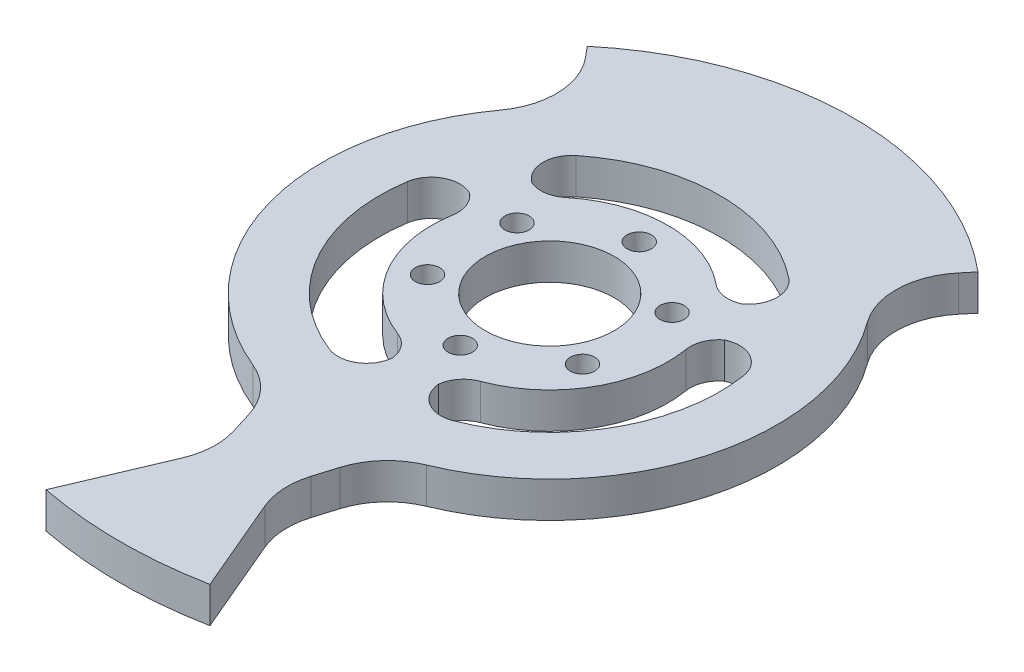
SolidWorks part; units mm, degrees
material "AISI Type A2 Tool Steel"
ref_plane "Front Plane" through (0, 0, 0) normal (0, 0, 1) x (1, 0, 0)
ref_plane "Top Plane" through (0, 0, 0) normal (0, 1, 0) x (1, 0, 0)
ref_plane "Right Plane" through (0, 0, 0) normal (1, 0, 0) x (0, 0, -1)
other "Center of Mass"
other "Bounding Box"
ref_plane "Default Plane" through (0, 2.286, 19.05) normal (0, -1, 0) x (-1, 0, 0)
sketch "Sketch1" plane through (0, 0, 0) normal (0, 1, 0) x (1, 0, 0)
  line L0 (0, -76.2) -> (0, -40.3225) construction
  line L1 (0, -40.3225) -> (0, -11.43) construction
  line L2 (0, -11.43) -> (0, 0) construction
  circle A0 centre (0, 0) radius 76.2 construction
  circle A1 centre (0, 0) radius 11.43
  arc A2 (0, -40.3225) -> (0, 40.3225) centre (0, 0) ccw
  arc A3 (0, 40.3225) -> (0, -76.2) centre (0, -17.9387) ccw construction
  arc A4 (0, 40.3225) -> (0, -40.3225) centre (0, 0) ccw
  dimension "D1" = 152.4
  dimension "D2" = 22.86
  dimension "D3" = 80.645
extrude "Boss-Extrude2" add sketch "Sketch1" along normal mid plane 6.35
sketch "Sketch9" plane through (0, 3.175, 0) normal (0, 1, 0) x (1, 0, 0)
  line L2 (-14.5396, -74.8) -> (-5.5514, -53.6249)
  line L3 (14.5396, -74.8) -> (5.5514, -53.6249)
  line L4 (0, -76.2) -> (0, 0) construction
  line L5 (-5.5514, -53.6249) -> (-10.0037, -39.0619)
  line L6 (5.5514, -53.6249) -> (10.0037, -39.0619)
  line L7 (-34.6536, 41.2986) -> (-25.9188, 30.8888)
  line L8 (34.6536, 41.2986) -> (25.9188, 30.8888)
  line L9 (0, 53.9115) -> (0, 0) construction
  line L10 (-5.5514, -53.6249) -> (0, -40.5467) construction
  line L11 (0, -40.5467) -> (5.5514, -53.6249) construction
  line L12 (-14.5396, -74.8) -> (0, 0) construction
  arc A5 (-14.5396, -74.8) -> (14.5396, -74.8) centre (0, 0) ccw
  arc A6 (-5.5514, -53.6249) -> (5.5514, -53.6249) centre (0, 0) ccw construction
  circle A7 centre (0, 0) radius 40.3225 construction
  arc A8 (-10.0037, -39.0619) -> (10.0037, -39.0619) centre (0, 0) ccw
  arc A9 (-34.6536, 41.2986) -> (34.6536, 41.2986) centre (0, 0) cw
  arc A10 (25.9188, 30.8888) -> (-25.9188, 30.8888) centre (0, 0) ccw
  dimension "D1" = 76.2
  dimension "D3" = 13.589
  dimension "D5" = 11
  dimension "D2" = 12
  dimension "D4" = 80
  dimension "D6" = 17
extrude "Boss-Extrude4" add sketch "Sketch9" against normal through all
sketch "Sketch6" plane through (0, 3.175, 0) normal (0, 1, 0) x (1, 0, 0)
  line L0 (-23.9377, 18.3511) -> (-15.7556, 13.8157)
  line L1 (15.7556, 13.8157) -> (23.9377, 18.3511)
  line L2 (0, 0) -> (-26.0927, 14.4634) construction
  line L3 (0, 0) -> (26.0927, 14.4634) construction
  line L4 (-23.9377, 18.3511) -> (-26.0927, 14.4634) construction
  line L5 (23.9377, 18.3511) -> (26.0927, 14.4634) construction
  line L6 (0, 0) -> (0, 40.3225) construction
  arc A0 (-15.7556, 13.8157) -> (15.7556, 13.8157) centre (0, 0) cw
  arc A1 (-23.9377, 18.3511) -> (23.9377, 18.3511) centre (0, 0) cw
  circle A2 centre (0, 0) radius 11.43 construction
  arc A4 (29.0716, 27.9418) -> (-0.0952, -40.3224) centre (0, 0) ccw construction
  arc A5 (10.0037, -39.0619) -> (25.9188, 30.8888) centre (0, 0) ccw construction
  dimension "D3" = 61
  dimension "D4" = 10.16
  dimension "D1" = 9.525
  dimension "D2" = 4.445
  dimension "D5" = 61
extrude "Cut-Extrude2" cut sketch "Sketch6" against normal through all
pattern_circular "CirPattern1" count 3 over 360 about axis through (0, 3.175, 0) along (0, -1, 0) of "Cut-Extrude2"
sketch "Sketch7" [suppressed] plane through (0, 6.35, 0) normal (0, 1, 0) x (1, 0, 0)
  line L0 (12.4559, 70.0208) -> (11.1213, 62.5185)
  line L1 (70.0208, -12.4559) -> (62.5185, -11.1213)
  line L2 (0, 0) -> (52.0712, 36.3433) construction
  line L3 (0, 0) -> (0, 63.5) construction
  line L4 (-6.2364, -4.3527) -> (0, 0) construction
  arc A0 (70.0208, -12.4559) -> (12.4559, 70.0208) centre (0, 0) ccw
  arc A1 (2.4423, -63.453) -> (0, 63.5) centre (0, 0) ccw construction
  arc A2 (62.5185, -11.1213) -> (11.1213, 62.5185) centre (0, 0) ccw
  dimension "D1" = 7.62
  dimension "D3" = 90
sketch "Sketch10" plane through (0, 3.175, 0) normal (0, 1, 0) x (1, 0, 0)
  line L0 (0, 20.955) -> (0, 15.875) construction
  line L1 (0, 15.875) -> (0, 11.43) construction
  circle A0 centre (0, 15.875) radius 2.159
  circle A1 centre (0, 15.875) radius 3.9624 construction
  circle A2 centre (0, 0) radius 11.43 construction
  arc A3 (4.0869, -20.5526) -> (19.8425, 6.7369) centre (0, 0) ccw construction
  dimension "D1" = 4.318
  dimension "D2" = 7.9248
  dimension "D3" = 15.875
extrude "Cut-Extrude3" cut sketch "Sketch10" against normal through all
pattern_circular "CirPattern8" count 6 over 360 about axis through (0, 3.175, 0) along (0, -1, 0) of "Cut-Extrude3" reverse direction yes
fillet "Fillet3" radius 5.08 12 edges at (-23.9377, 0, -18.3511) (23.9377, 0, -18.3511) (15.7556, 0, -13.8157) (-15.7556, 0, -13.8157) (3.9237, 0, 29.9062) (27.8614, 0, -11.5551) (19.8425, 0, -6.7369) (4.0869, 0, 20.5526) (-3.9237, 0, 29.9062) (-4.0869, 0, 20.5526) (-19.8425, 0, -6.7369) (-27.8614, 0, -11.5551)
other "Center of Mass Reference Point2"
fillet "Fillet4" radius 12.7 6 edges at (-5.5514, 0, 53.6249) (-10.0037, 0, 39.0619) (5.5514, 0, 53.6249) (10.0037, 0, 39.0619) (25.9188, 0, -30.8888) (-25.9188, 0, -30.8888)
sketch "Sketch13" plane through (0, 3.175, 0) normal (0, 1, 0) x (1, 0, 0)
  arc B0 (-18.8515, 23.5457) -> (18.8515, 23.5457) centre (0, 0) cw
  arc B1 (18.8515, 23.5457) -> (18.5756, 15.4086) centre (15.6765, 19.5801) cw
  arc B2 (18.5756, 15.4086) -> (13.3403, 16.1601) centre (16.5743, 20.0777) cw
  arc B3 (13.3403, 16.1601) -> (-13.3403, 16.1601) centre (0, 0) ccw
  arc B4 (-13.3403, 16.1601) -> (-18.5756, 15.4086) centre (-16.5743, 20.0777) cw
  arc B5 (-18.5756, 15.4086) -> (-18.8515, 23.5457) centre (-15.6765, 19.5801) cw
  arc B6 (-20.6652, 3.473) -> (-22.632, 8.3827) centre (-25.6749, 4.3149) ccw
  arc B7 (-22.632, 8.3827) -> (-29.8169, 4.553) centre (-24.7951, 3.7862) ccw
  arc B8 (-29.8169, 4.553) -> (-10.9654, -28.0987) centre (0, 0) ccw
  arc B9 (-10.9654, -28.0987) -> (-4.0564, -23.7912) centre (-9.1186, -23.3663) ccw
  arc B10 (-4.0564, -23.7912) -> (-7.3249, -19.6331) centre (-9.1007, -24.3926) ccw
  arc B11 (-7.3249, -19.6331) -> (-20.6652, 3.473) centre (0, 0) cw
  arc B12 (7.3249, -19.6331) -> (4.0564, -23.7912) centre (9.1007, -24.3926) ccw
  arc B13 (4.0564, -23.7912) -> (10.9654, -28.0987) centre (9.1186, -23.3663) ccw
  arc B14 (10.9654, -28.0987) -> (29.8169, 4.553) centre (0, 0) ccw
  arc B15 (29.8169, 4.553) -> (22.632, 8.3827) centre (24.7951, 3.7862) ccw
  arc B16 (22.632, 8.3827) -> (20.6652, 3.473) centre (25.6749, 4.3149) ccw
  arc B17 (20.6652, 3.473) -> (7.3249, -19.6331) centre (0, 0) cw
  circle B18 centre (0, 0) radius 11.43
  circle B19 centre (13.7482, 7.9375) radius 2.159
  circle B20 centre (0, 15.875) radius 2.159
  circle B21 centre (-13.7482, 7.9375) radius 2.159
  circle B22 centre (-13.7482, -7.9375) radius 2.159
  circle B23 centre (0, -15.875) radius 2.159
  circle B24 centre (13.7482, -7.9375) radius 2.159
sketch_block_instance "Block1-1"
sketch_block "Block1"
equation "\"Unit Measure\"= \"BoundingVolume\" / \"Thickness\"'in^2"
